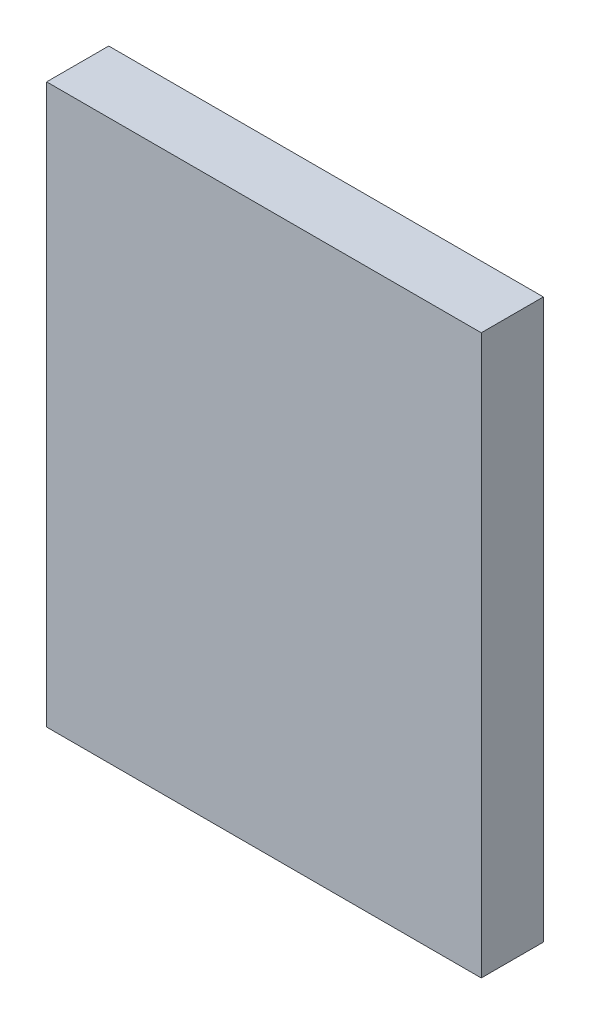
SolidWorks part; units mm, degrees
ref_plane "Front Plane" through (0, 0, 0) normal (0, 0, 1) x (1, 0, 0)
ref_plane "Top Plane" through (0, 0, 0) normal (0, 1, 0) x (1, 0, 0)
ref_plane "Right Plane" through (0, 0, 0) normal (1, 0, 0) x (0, 0, -1)
sketch "Sketch1" plane through (0, 0, 0) normal (0, 0, 1) x (1, 0, 0)
  line L1 (-19.6138, 16.2133) -> (15.3862, 16.2133)
  line L2 (-19.6138, 16.2133) -> (-19.6138, -28.7867)
  line L3 (-19.6138, -28.7867) -> (15.3862, -28.7867)
  line L4 (15.3862, 16.2133) -> (15.3862, -28.7867)
  dimension "D1" = 35
  dimension "D2" = 45
extrude "Boss-Extrude1" add sketch "Sketch1" along normal blind 5
